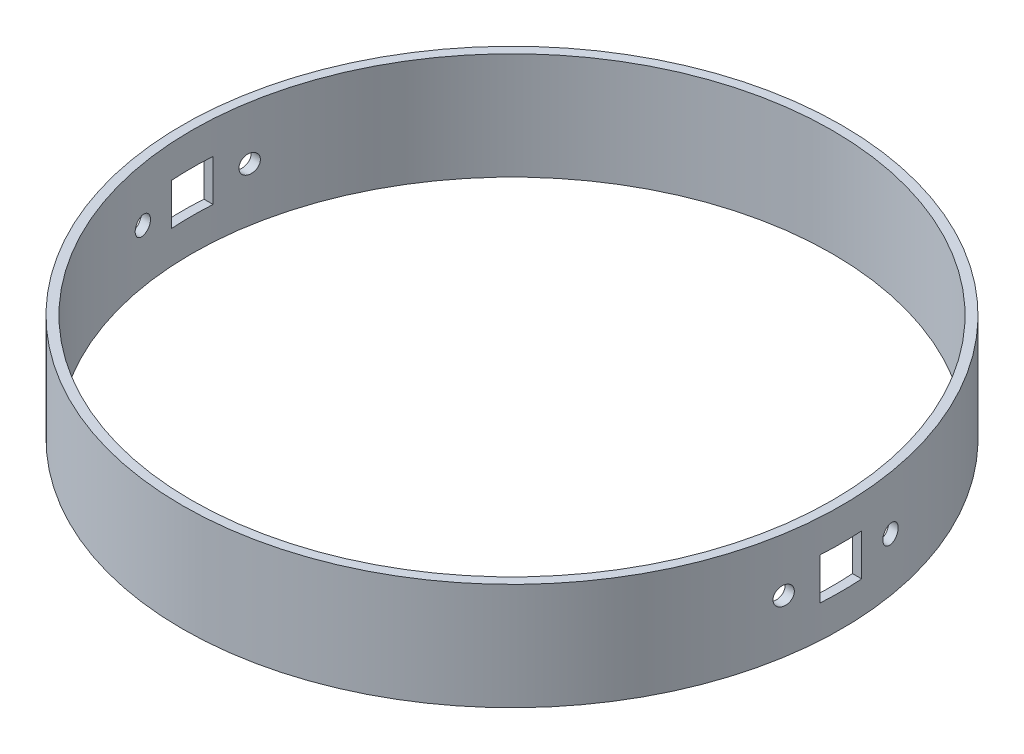
SolidWorks part; units mm, degrees
material "A-Glass Fiber"
ref_plane "Front Plane" through (0, 0, 0) normal (0, 0, 1) x (1, 0, 0)
ref_plane "Top Plane" through (0, 0, 0) normal (0, 1, 0) x (1, 0, 0)
ref_plane "Right Plane" through (0, 0, 0) normal (1, 0, 0) x (0, 0, -1)
sketch "Sketch1" plane through (0, 0, 0) normal (0, 1, 0) x (1, 0, 0)
  circle A0 centre (0, 0) radius 78.359
  circle A1 centre (0, 0) radius 76.1746
  dimension "D1" = 156.718
  dimension "D2" = 152.3492
extrude "Boss-Extrude1" add sketch "Sketch1" along normal blind 25.4
sketch "Sketch2" plane through (0, 0, 0) normal (1, 0, 0) x (0, 0, -1)
  line L0 (-78.359, 0) -> (78.359, 0) construction
  line L7 (0, 12.7) -> (0, 14.52) construction
  line L12 (4.953, 7.747) -> (-4.953, 7.747)
  line L13 (0, 25.4) -> (0, 0) construction
  line L14 (76.1746, 25.4) -> (-76.1746, 25.4) construction
  line L15 (-78.359, 0) -> (78.359, 0)
  line L16 (76.1746, 25.4) -> (-76.1746, 25.4)
  line L17 (-28.7231, 12.7) -> (26.1298, 12.7) construction
  line L25 (4.953, 7.747) -> (4.953, 17.653)
  line L26 (4.953, 17.653) -> (-4.953, 17.653)
  line L27 (-4.953, 7.747) -> (-4.953, 17.653)
  line L28 (4.953, 7.747) -> (-4.953, 17.653) construction
  line L29 (4.953, 17.653) -> (-4.953, 7.747) construction
  circle A0 centre (-12.7, 12.7) radius 2.1831
  circle A1 centre (12.7, 12.7) radius 2.1831
  point P0 (0, 9.85)
  point P14 (0, 3.175)
  point P27 (0, 12.7)
  dimension "D4" = 9.906
  dimension "D8" = 4.3663
  dimension "D1" = 12.7
  dimension "D5" = 9.906
extrude "Cut-Extrude1" cut sketch "Sketch2" along normal through all both and the other way through all contours L25 L12 L27 L26 | A1 | A0
ref_plane "Plane1" through (0, 0, 0) normal (0.9973, 0, 0.0728) x (0, -1, 0)
ref_plane "Plane2" through (0, 12.7, 0) normal (0, 1, 0) x (1, 0, 0)
mirror "Mirror2" about plane through (0, 0, 0) normal (1, 0, 0) of "Cut-Extrude1", "Boss-Extrude1" second plane through (0, 12.7, 0) second plane normal (0, 1, 0)
equation "\"Bodytube_OD\" = 6.17in"
equation "\"Bodytube_ID\" = 5.998in"
equation "\"D1@Sketch1\"=\"Bodytube_OD\""
equation "\"D2@Sketch1\"= \"Bodytube_ID\""
equation "\"Camera_Cutout_Width\"=10mm"
equation "\"Camera_Cutout_Height\"=7mm"
equation "\"Fwd_Tube_Length\" = 40in"
equation "\"BKHD_Screw_Diam\"= 3.5mm"
equation "\"Fwd_BKHD_From_Top\" = 18in"
equation "\"Shear_Screw_Diameter\" = 0.086in"
equation "\"Shear_Screw_Coupler_Location\" = 4.5in"
equation "\"Motor_OD\" = 4in"
equation "\"Mid_Coupler_Length\" = 13in"
equation "\"Aft_Section_Length\"= 39in"
equation "\"AB_Coupler_OD_Length\"= 1in"
equation "\"AB_Coupling_Section_Length\"= 0.375in"
equation "\"AB_Coupler_Length\"= \"AB_Coupler_OD_Length\" + \"AB_Coupling_Section_Length\" * 2"
equation "\"Cutout_Angle\" = 80"
equation "\"AB_Paddle_Height\" = 0.375in"
equation "\"AB_Coupler_Num_Screws\"= 4"
equation "\"AB_BKHD_Thickness\" = 0.375in"
equation "\"AB_Mount_From_Bottom\" = 23.175in"
equation "\"Num_Cutouts\" = 3"
equation "\"AB_Coupler_OD\"= 6.17in"
equation "\"AB_Coupler_ID\"= 5.75in"
equation "\"AB_Coupler_Surface_Diameter\"= 5.998in"
equation "\"AB_Coupling_Screw_Diameter\"= 0.15748in"
equation "\"AB_Central_Bushing_Length\" = .4724in"
equation "\"Lead_Screw_Dist\" = 3.4in"
equation "\"Lead_Screw_Diam\" = 0.386in"
equation "\"Lead_Screw_Length\" = (\"Mid_Coupler_Length\" + 2*0.375in + 2*0.5in)"
equation "\"Paddle_Pin_Offset\" = .25in"
equation "\"Paddle_Pin_Radius\" = 2.25in"
equation "\"SS_Paddle_Pin_Radius\" = 2.25*0.66in"
equation "\"Paddle_Gear_OD\" = 3.2in"
equation "\"Drive_Gear_OD\" = 1.7in"
equation "\"Fin_Thickness\"= .118in"
equation "\"Guiderail_Cutout_Diameter\"= 1.5in"
equation "\"DB9_Hole_Dist\" = 25mm"
equation "\"DB9_Relief_Width\" = 0.47in"
equation "\"DB9_Relief_Hole_Offset\" = 0.09in"
equation "\"Airbrakes_Wire_Hole_Dia\" = .25in"
equation "\"Airbrakes_Wire_Hole_Dist\" = 1.1in"
equation "\"Servo_Gear_Offset\" = 0.5in"
equation "\"FWD_Shear_Screw_Dist\" = 1.5in"
equation "\"Camera_Screw_Dia\" = 0.216535"
equation "\"Camera_Hole_Angle\" = atn ( 2 / 3 * tan ( 12.5deg ) )"
equation "\"Coupler_OD\" = 5.998"
equation "\"Coupler_ID\" = 5.8"
equation "\"Mounting_Bracket_Centerhole_DIA\" = 0.4in"
equation "\"Drive_Gear_Shaft_DIA\" = \"Mounting_Bracket_Centerhole_DIA\" - 0.02in"
equation "\"Drive_Gear_Fillet\" = 0.22in"
equation "\"Drive_Gear_ID\" = 0.62in"
equation "\"Drive_Gear_Offset\" = 0.01in"
